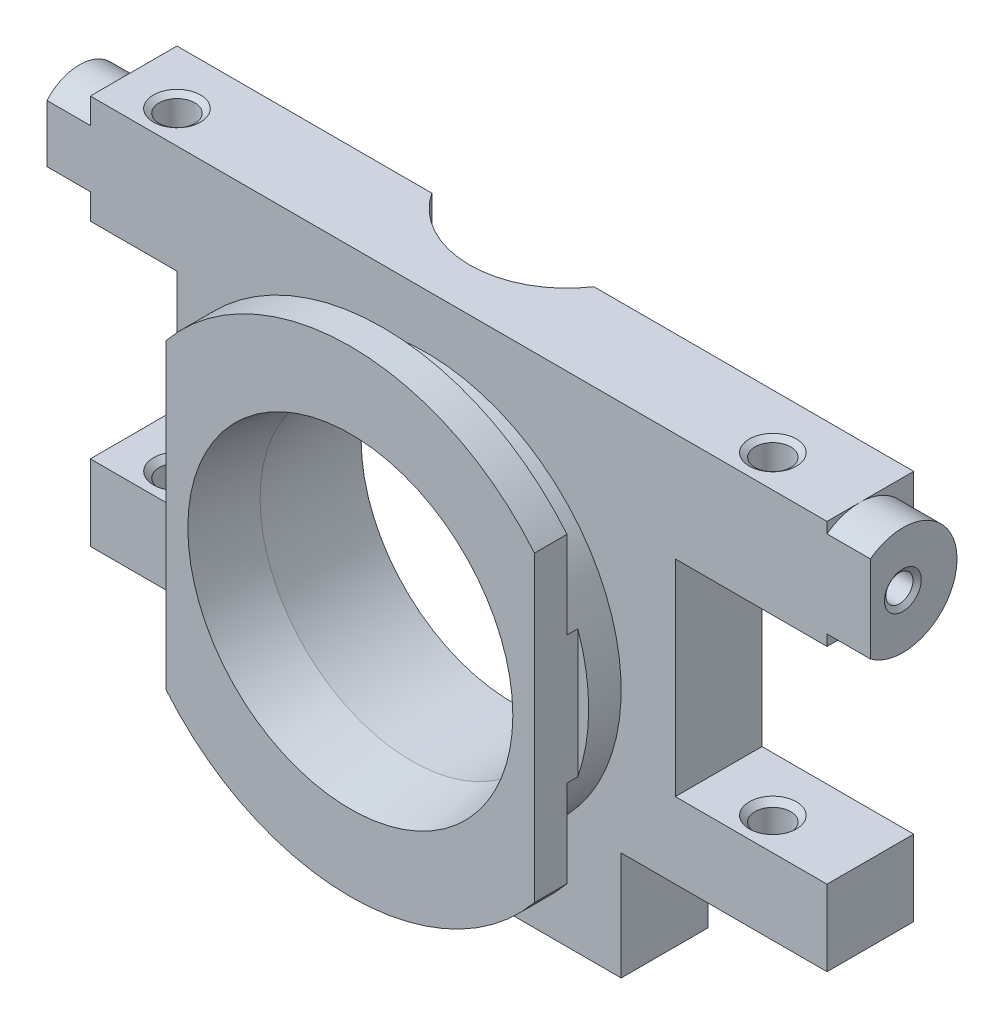
SolidWorks part; units mm, degrees
material "1060 Сплав"
ref_plane "Спереди" through (0, 0, 0) normal (0, 0, 1) x (1, 0, 0)
ref_plane "Сверху" through (0, 0, 0) normal (0, 1, 0) x (1, 0, 0)
ref_plane "Справа" through (0, 0, 0) normal (1, 0, 0) x (0, 0, -1)
sketch "Эскиз1" plane through (0, 0, 0) normal (0, 0, 1) x (1, 0, 0)
  line L1 (0, 0) -> (76, 0)
  line L2 (0, 0) -> (0, 46)
  line L3 (0, 46) -> (76, 46)
  line L4 (76, 0) -> (76, 46)
  dimension "D1" = 76
  dimension "D2" = 46
extrude "Бобышка-Вытянуть1" add sketch "Эскиз1" along normal blind 15
sketch "Эскиз2" plane through (0, 0, 15) normal (0, 0, 1) x (1, 0, 0)
  line L1 (0, 46) -> (0, 0) construction
  line L2 (76, 46) -> (0, 46) construction
  circle A0 centre (35, 23) radius 14
  dimension "D3" = 28
  dimension "D1" = 23
  dimension "D2" = 35
extrude "Вырез-Вытянуть1" cut sketch "Эскиз2" against normal up to next contours A0 region at (35, 23, 15)
ref_axis "Ось1" through (35, 23, 0) along (0, 0, 1)
ref_plane "Плоскость1" through (0, 23, 0) normal (0, 1, 0) x (-1, 0, 0)
sketch "Эскиз3" plane through (0, 0, 15) normal (0, 0, 1) x (1, 0, 0)
  line L0 (0, 46) -> (0, 0) construction
  line L1 (4, 10) -> (17, 10)
  line L2 (17, 10) -> (17, 0)
  line L3 (0, 0) -> (76, 0) construction
  line L4 (53, 0) -> (53, 10)
  line L5 (53, 10) -> (72, 10)
  line L6 (76, 0) -> (76, 46) construction
  line L7 (76, 46) -> (0, 46) construction
  line L8 (4, 17) -> (12, 17)
  line L9 (12, 17) -> (12, 36)
  line L10 (12, 36) -> (0, 36)
  line L11 (76, 36) -> (58, 36)
  line L12 (58, 36) -> (58, 17)
  line L13 (58, 17) -> (72, 17)
  line L14 (4, 17) -> (4, 10)
  line L15 (72, 17) -> (72, 10)
  line M2 (0, 46) -> (0, 0)
  line M3 (0, 0) -> (76, 0)
  line M4 (76, 0) -> (76, 46)
  dimension "D1" = 36
  dimension "D2" = 36
  dimension "D3" = 17
  dimension "D4" = 12
  dimension "D5" = 10
  dimension "D6" = 19
  dimension "D7" = 18
  dimension "D8" = 4
  dimension "D9" = 4
extrude "Вырез-Вытянуть3" cut sketch "Эскиз3" against normal through all contours L14 L8 L9 L10 L2 L1 M2 M3 | L13 L15 L5 L4 L11 L12 M3 M4 region at (66.3683, 17.6517, 15) region at (6.7347, 17.0657, 15)
sketch "Эскиз4" plane through (0, 46, 0) normal (0, 1, 0) x (1, 0, 0)
  line L0 (76, 0) -> (0, 0) construction
  line L1 (35, -4) -> (17.1507, -4) construction
  line L3 (35, 0) -> (35, -15) construction
  arc A0 (27.5167, 0) -> (42.4833, 0) centre (35, 5) ccw
  line M1 (76, 0) -> (0, 0)
  dimension "D1" = 9
  dimension "D2" = 4
extrude "Вырез-Вытянуть4" cut sketch "Эскиз4" against normal up to next contours A0 M1 region at (35, 46, 1.635)
sketch "Эскиз5" plane through (0, 23, 0) normal (0, 1, 0) x (-1, 0, 0)
  line L0 (-76, 15) -> (0, 15) construction
  line L1 (-13, 15) -> (15, 15)
  line L2 (-13, 15) -> (-13, 12)
  line L3 (15, 8) -> (-17, 8)
  line L4 (15, 15) -> (15, 8)
  line L5 (-35, 0) -> (-35, 15) construction
  line L6 (-27.5167, 0) -> (0, 0) construction
  line L7 (-20, 15) -> (-21.5647, 6.1262)
  line L8 (-13, 12) -> (-17, 12)
  line L9 (-17, 12) -> (-17, 8)
  line L10 (-21.5647, 6.1262) -> (-21.5647, 15)
  line L11 (-21.5647, 15) -> (-20, 15)
  dimension "D1" = 50
  dimension "D2" = 22
  dimension "D3" = 8
  dimension "D4" = 18
  dimension "D5" = 3
  dimension "D6" = 10
  dimension "D7" = 15
revolve "Вырез-Повернуть1" cut sketch "Эскиз5" angle 360 about axis through (35, 23, 0) along (0, 0, 1) region at (0.2075, 23, 11.3868) region at (21.0431, 23, 12.0421)
hole_wizard "Отверстие обработанное метчиком M41" positions "Эскиз7" profile "Эскиз6" tap size "M4" standard "DIN" end condition up to next
sketch "Эскиз7" plane through (0, 46, 0) normal (0, 1, 0) x (-1, 0, 0)
  line L0 (-76, 8) -> (-76, 0) construction
  line L2 (-4, 0) -> (-17, 0) construction
  point P0 (-9, 5)
  point P1 (-64, 5)
  dimension "D1" = 55
  dimension "D2" = 12
  dimension "D3" = 5
sketch "Эскиз6" plane through (9, 46, 5) normal (1, 0, 0) x (0, 0, 1)
  line L0 (0, 0) -> (0, 10)
  line L1 (0, 10) -> (2.175, 10)
  line L2 (1.65, 9.475) -> (1.65, 0.3676)
  line L3 (1.65, 0.3676) -> (2.175, 0)
  line L5 (2.175, 0) -> (0, 0)
  line L6 (-1.65, 0.3676) -> (-2.175, 0) construction
  line L7 (2.175, 10) -> (1.65, 9.475)
  line L8 (-2.175, 10) -> (-1.65, 9.475) construction
  line L11 (0, -6.35) -> (0, 107.95) construction
  dimension "Диаметр резьбы" = 3.3
  dimension "Глубина проходного сверла" = 10
  dimension "Диаметр передней зенковки" = 4.35
  dimension "Угол передней зенковки" = 110
  dimension "Диаметр задней зенковки" = 4.35
  dimension "Угол задней зенковки" = 90
hole_wizard "Отверстие обработанное метчиком M42" positions "Эскиз9" profile "Эскиз8" tap size "M4" standard "DIN" end condition up to next
sketch "Эскиз9" plane through (0, 10, 0) normal (0, -1, 0) x (1, 0, 0)
  line L3 (4, 0) -> (17, 0) construction
  line L4 (53, 0) -> (53, 8) construction
  point P0 (64, 5)
  point P1 (9, 5)
  dimension "D1" = 55
  dimension "D2" = 11
  dimension "D3" = 5
sketch "Эскиз8" plane through (64, 10, 5) normal (1, 0, 0) x (0, 0, -1)
  line L0 (0, 0) -> (0, 7)
  line L1 (0, 7) -> (2.175, 7)
  line L2 (1.65, 6.475) -> (1.65, 0.3676)
  line L3 (1.65, 0.3676) -> (2.175, 0)
  line L5 (2.175, 0) -> (0, 0)
  line L6 (-1.65, 0.3676) -> (-2.175, 0) construction
  line L7 (2.175, 7) -> (1.65, 6.475)
  line L8 (-2.175, 7) -> (-1.65, 6.475) construction
  line L11 (0, -6.35) -> (0, 107.95) construction
  dimension "Диаметр резьбы" = 3.3
  dimension "Глубина проходного сверла" = 7
  dimension "Диаметр передней зенковки" = 4.35
  dimension "Угол передней зенковки" = 110
  dimension "Диаметр задней зенковки" = 4.35
  dimension "Угол задней зенковки" = 90
hole_wizard "Отверстие обработанное метчиком M31" positions "Эскиз11" profile "Эскиз10" tap size "M3" standard "DIN" end condition up to next
sketch "Эскиз11" plane through (0, 0, 0) normal (-1, 0, 0) x (0, 0, 1)
  line L0 (8, 46) -> (0, 46) construction
  line L1 (0, 46) -> (0, 36) construction
  point P0 (5, 41)
  dimension "D1" = 5
  dimension "D2" = 5
sketch "Эскиз10" plane through (0, 41, 5) normal (0, 1, 0) x (0, 0, 1)
  line L0 (0, 0) -> (0, 7.35)
  line L1 (0, 7.35) -> (1.25, 7.35)
  line L2 (1.25, 7.35) -> (1.25, 0.3151)
  line L3 (1.25, 0.3151) -> (1.7, 0)
  line L5 (1.7, 0) -> (0, 0)
  line L6 (-1.25, 0.3151) -> (-1.7, 0) construction
  line L11 (0, -6.35) -> (0, 107.95) construction
  dimension "Диаметр проходного сверла" = 2.5
  dimension "Глубина проходного сверла" = 7.35
  dimension "Диаметр передней зенковки" = 3.4
  dimension "Угол передней зенковки" = 110
cosmetic thread "Отверстие резьбы1" parameters "D2"=3
hole_wizard "Отверстие обработанное метчиком M32" positions "Эскиз13" profile "Эскиз12" tap size "M3" standard "DIN" end condition up to next
sketch "Эскиз13" plane through (76, 0, 0) normal (1, 0, 0) x (0, 0, -1)
  point P0 (-5, 41)
sketch "Эскиз12" plane through (76, 41, 5) normal (0, 1, 0) x (0, 0, -1)
  line L0 (0, 0) -> (0, 10.35)
  line L1 (0, 10.35) -> (1.25, 10.35)
  line L2 (1.25, 10.35) -> (1.25, 0.3151)
  line L3 (1.25, 0.3151) -> (1.7, 0)
  line L5 (1.7, 0) -> (0, 0)
  line L6 (-1.25, 0.3151) -> (-1.7, 0) construction
  line L11 (0, -6.35) -> (0, 107.95) construction
  dimension "Диаметр проходного сверла" = 2.5
  dimension "Глубина проходного сверла" = 10.35
  dimension "Диаметр передней зенковки" = 3.4
  dimension "Угол передней зенковки" = 110
cosmetic thread "Отверстие резьбы2" parameters "D2"=3
ref_axis "Ось2" through (8.0068, 41, 5) along (-1, 0, 0)
ref_plane "Плоскость2" through (0, 0, 5) normal (0, 0, -1) x (-1, 0, 0)
sketch "Эскиз15" plane through (0, 0, 5) normal (0, 0, -1) x (-1, 0, 0)
  line L0 (-4, 17) -> (-4, 10) construction
  line L1 (-4, 30.8018) -> (0, 30.8018)
  line L2 (-4, 30.8018) -> (-4, 37)
  line L3 (-4, 37) -> (0, 37)
  line L4 (0, 30.8018) -> (0, 37)
  line L5 (-72, 17) -> (-72, 10) construction
  line L6 (-76, 36) -> (-72, 36)
  line L7 (-76, 36) -> (-76, 30.8018)
  line L8 (-76, 30.8018) -> (-72, 30.8018)
  line L9 (-72, 36) -> (-72, 30.8018)
  line L10 (0, 46) -> (0, 36) construction
  line L11 (-8.0068, 41) -> (-0.3151, 41) construction
  line L12 (-76, 36) -> (-76, 46) construction
  dimension "D1" = 4
  dimension "D2" = 5
revolve "Вырез-Повернуть2" cut sketch "Эскиз15" angle 360 about axis through (8.0068, 41, 5) along (-1, 0, 0)
sketch "Эскиз16" plane through (0, 0, 15) normal (0, 0, 1) x (1, 0, 0)
  line L0 (18, 36.9642) -> (18, 9.0358)
  line L1 (52, 36.9642) -> (52, 9.0358)
  circle A0 centre (35, 23) radius 22 construction
  circle M1 centre (35, 23) radius 22
  dimension "D1" = 34
extrude "Вырез-Вытянуть5" cut sketch "Эскиз16" against normal blind 4 contours L0 M1 | L1 M1 region at (15.9791, 23, 15) region at (54.0209, 23, 15)
